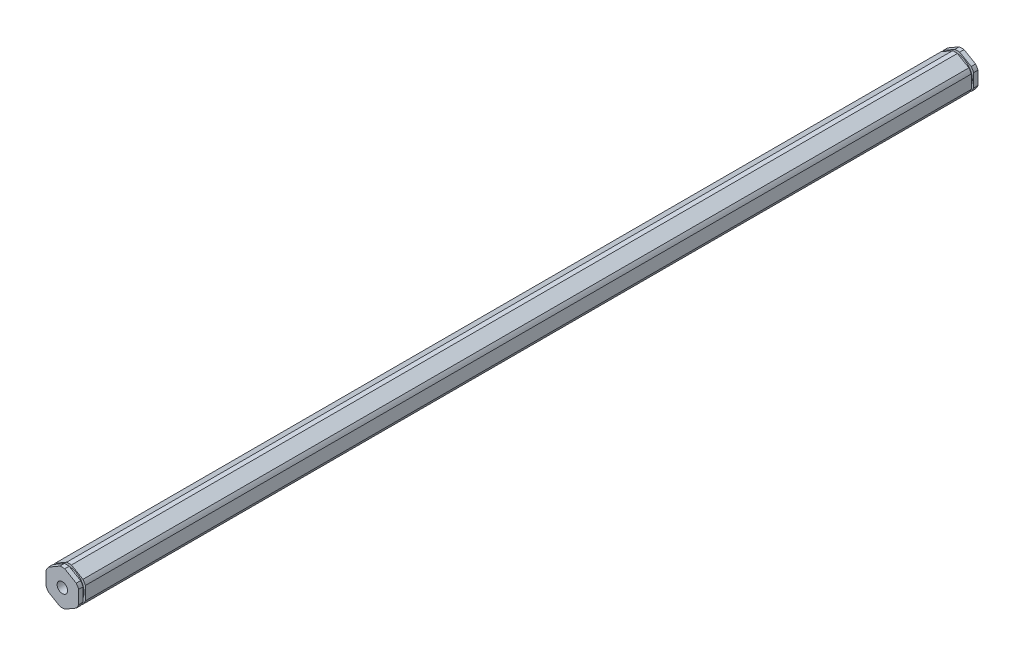
SolidWorks part; units mm, degrees
ref_plane "Front Plane" through (0, 0, 0) normal (0, 0, 1) x (1, 0, 0)
ref_plane "Top Plane" through (0, 0, 0) normal (0, 1, 0) x (1, 0, 0)
ref_plane "Right Plane" through (0, 0, 0) normal (1, 0, 0) x (0, 0, -1)
sketch "Sketch1" plane through (0, 0, 0) normal (0, 0, 1) x (1, 0, 0)
  line L1 (0, 7.3323) -> (-6.35, 3.6662)
  line L2 (-6.35, 3.6662) -> (-6.35, -3.6662)
  line L3 (-6.35, -3.6662) -> (0, -7.3323)
  line L4 (0, -7.3323) -> (6.35, -3.6662)
  line L5 (6.35, -3.6662) -> (6.35, 3.6662)
  line L6 (6.35, 3.6662) -> (0, 7.3323)
  circle A0 centre (0, 0) radius 6.35 construction
  circle A1 centre (0, 0) radius 6.858
  dimension "D1" = 12.7
  dimension "D2" = 13.716
extrude "Boss-Extrude1" add sketch "Sketch1" along normal mid plane 349.8215 contours L5 A1 L6 L1 L2 L3 L4 region at (0, 0, 0)
hole_wizard "#10-32 Tapped Hole1" positions "3DSketch1" profile "Sketch2" tap size "#10-32" standard "ANSI Inch"
sketch3d "3DSketch1"
  line L0 (0, 0, 174.9108) -> (0, 0, -174.9108) construction
  line L1 (0, 0, 174.9108) -> (0, 0, -174.9108) construction
  point P0 (0, 0, 174.9108)
  point P4 (0, 0, -174.9108)
sketch "Sketch2" plane through (0, 0, 174.9108) normal (1, 0, 0) x (0, -1, 0)
  line L0 (0, 0) -> (0, 17.5608)
  line L1 (0, 17.5608) -> (2.0193, 16.3474)
  line L2 (2.0193, 16.3474) -> (2.0193, 0)
  line L5 (2.0193, 0) -> (0, 0)
  line L10 (0, 17.5608) -> (-2.0193, 16.3474) construction
  line L11 (0, -6.35) -> (0, 107.95) construction
  dimension "Tap Drill Dia." = 4.0386
  dimension "Tap Drill Depth" = 16.3474
  dimension "Drill Angle" = 118
cosmetic thread "Hole Thread1" parameters "D1"=13.97, "D2"=4.826
cosmetic thread "Hole Thread2" parameters "D1"=13.97, "D2"=4.826
sketch "Sketch3" plane through (0, 0, 0) normal (1, 0, 0) x (0, 0, -1)
  line L0 (-175.1574, 0) -> (-171.1173, 0) construction
  line L1 (174.9108, 6.858) -> (-174.9108, 6.858) construction
  line L2 (-173.1962, 6.858) -> (-172.3072, 6.858)
  line L3 (-173.1962, 6.858) -> (-173.1962, 5.8547)
  line L4 (-173.1962, 5.8547) -> (-172.3072, 5.8547)
  line L5 (-172.3072, 6.858) -> (-172.3072, 5.8547)
  dimension "D1" = 0.889
  dimension "D2" = 5.8547
  dimension "D3" = 1.7145
revolve "Cut-Revolve1" cut sketch "Sketch3" angle 360 about L0
mirror "Mirror1" about plane through (0, 0, 0) normal (0, 0, 1) of "Cut-Revolve1"
